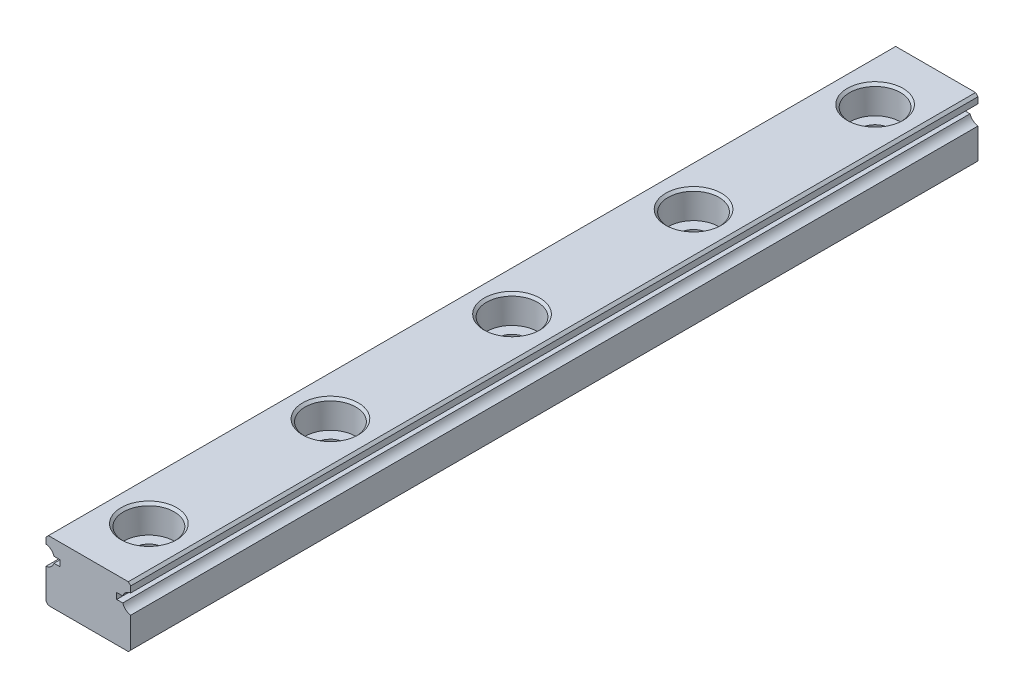
SolidWorks part; units mm, degrees
ref_plane "Спереди" through (0, 0, 0) normal (0, 0, 1) x (1, 0, 0)
ref_plane "Сверху" through (0, 0, 0) normal (0, 1, 0) x (1, 0, 0)
ref_plane "Справа" through (0, 0, 0) normal (1, 0, 0) x (0, 0, -1)
sketch "Sketch1" plane through (0, 0, 0) normal (0, 0, 1) x (1, 0, 0)
  line L0 (0, 0) -> (0, 4.3706) construction
  line L1 (-3.3, -2.5) -> (3.3, -2.5)
  line L2 (-3.5, -2.3) -> (-3.5, 0.2063)
  line L3 (-3.3, 2.5) -> (3.3, 2.5)
  line L4 (3.5, -2.3) -> (3.5, 0.2063)
  line L5 (-3.5, -2.5) -> (3.5, 2.5) construction
  line L6 (-3.5, 2.5) -> (3.5, -2.5) construction
  line L7 (-3.5, 1.7937) -> (-3.5, 2.3)
  line L8 (3.5, 1.7937) -> (3.5, 2.3)
  line L9 (-3.5, -2.3) -> (-3.3, -2.5)
  line L10 (3.3, -2.5) -> (3.5, -2.3)
  line L11 (3.3, 2.5) -> (3.5, 2.3)
  line L12 (-3.5, 2.3) -> (-3.3, 2.5)
  line L13 (2.8401, 0.75) -> (2.3401, 0.75)
  line L14 (-2.8401, 0.75) -> (-2.3401, 0.75)
  line L15 (2.3401, 0.75) -> (2.3401, 1.25)
  line L16 (-2.8401, 1.25) -> (-2.3401, 1.25)
  line L17 (-2.3401, 0.75) -> (-2.3401, 1.25)
  line L18 (2.8401, 1.25) -> (2.3401, 1.25)
  arc A0 (-3.5, 1.7937) -> (-2.8401, 1.25) centre (-3.6, 1) cw
  arc A1 (3.5, 1.7937) -> (2.8401, 1.25) centre (3.6, 1) ccw
  arc A2 (-2.8401, 0.75) -> (-3.5, 0.2063) centre (-3.6, 1) cw
  arc A3 (2.8401, 0.75) -> (3.5, 0.2063) centre (3.6, 1) ccw
  point P0 (0, 0)
  dimension "D4" = 0.8
  dimension "D5" = 0.1
  dimension "D1" = 7
  dimension "D2" = 5
  dimension "D3" = 1.5
  dimension "D6" = 0.5
  dimension "D7" = 0.5
extrude "Extrude1" add sketch "Sketch1" along normal blind 70
sketch "Sketch2" plane through (0, 2.5, 0) normal (0, 1, 0) x (1, 0, 0)
  line L0 (0, 0) -> (0, -5) construction
  circle A0 centre (0, -5) radius 1.2
  circle A1 centre (0, -5) radius 2.1
  dimension "D1" = 2.4
  dimension "D2" = 4.2
  dimension "D3" = 5
extrude "Extrude2" cut sketch "Sketch2" against normal up to next contours A0 region at (0, 2.5, 5)
extrude "Extrude4" cut sketch "Sketch" against normal blind 2.3
sketch "Sketch" plane through (0, 2.5, 0) normal (0, 1, 0) x (1, 0, 0) same geometry as "Sketch2"
chamfer "Chamfer1" distance 0.2 angle 45 2 edges at (0, -2.5, 6.2) (0, 2.5, 7.1)
pattern_linear "LPattern1" count 5 spacing 15 along (0, 0, 1) of "Extrude4", "Chamfer1", "Extrude2"
